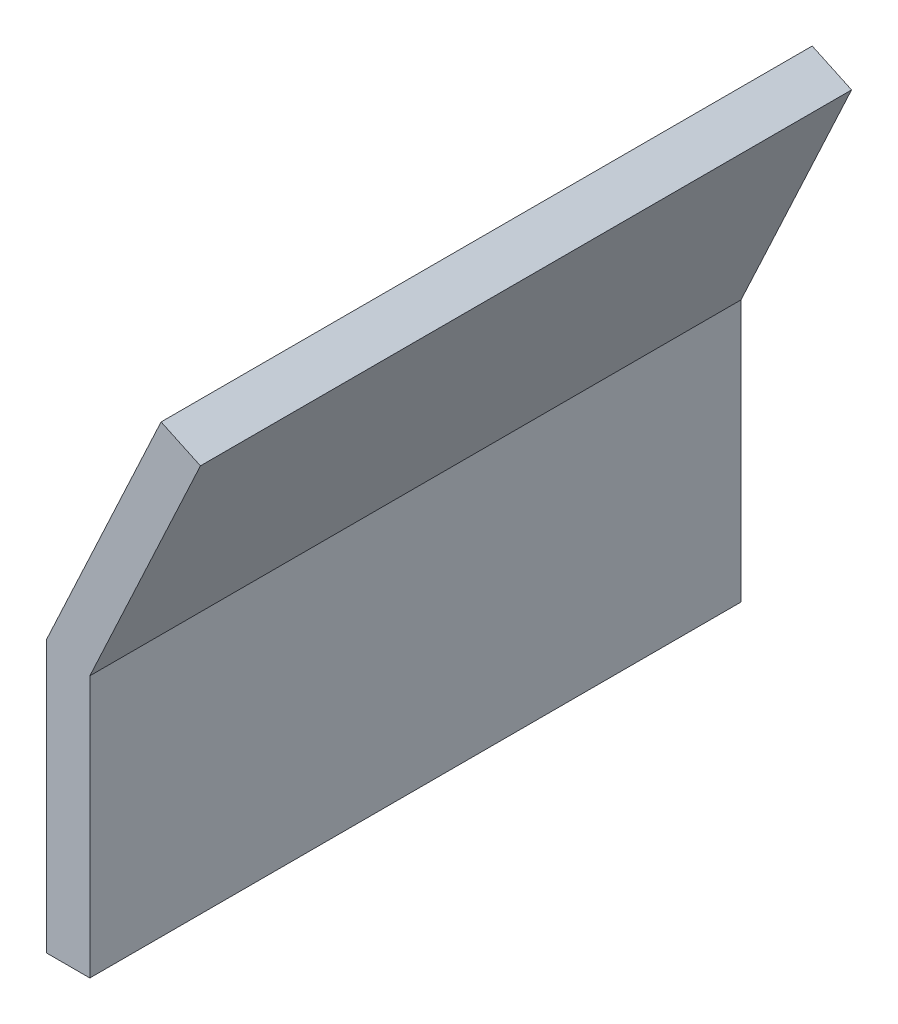
SolidWorks part; units mm, degrees
material "PLA"
ref_plane "Front Plane" through (0, 0, 0) normal (0, 0, 1) x (1, 0, 0)
ref_plane "Top Plane" through (0, 0, 0) normal (0, 1, 0) x (1, 0, 0)
ref_plane "Right Plane" through (0, 0, 0) normal (1, 0, 0) x (0, 0, -1)
sketch "Sketch1" plane through (0, 0, 0) normal (0, 0, 1) x (1, 0, 0)
  line L0 (0, 0) -> (21.1309, 45.3154)
  line L1 (0, 0) -> (0, -50)
  line L2 (8, -1.7736) -> (28.3814, 41.9344)
  line L3 (8, -1.7736) -> (8, -50)
  line L4 (21.1309, 45.3154) -> (28.3814, 41.9344)
  line L5 (0, -50) -> (8, -50)
  dimension "D1" = 50
  dimension "D2" = 50
  dimension "D3" = 155
  dimension "D4" = 8
extrude "Boss-Extrude1" add sketch "Sketch1" along normal mid plane 120
